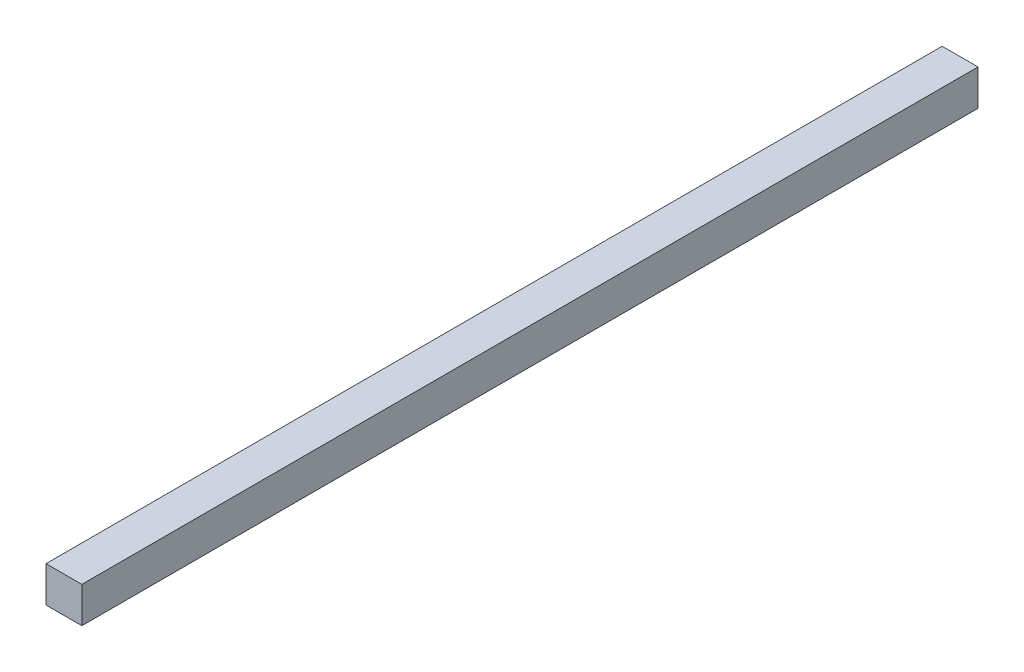
SolidWorks part; units mm, degrees
ref_plane "Front Plane" through (0, 0, 0) normal (0, 0, 1) x (1, 0, 0)
ref_plane "Top Plane" through (0, 0, 0) normal (0, 1, 0) x (1, 0, 0)
ref_plane "Right Plane" through (0, 0, 0) normal (1, 0, 0) x (0, 0, -1)
sketch "Sketch1" plane through (0, 0, 0) normal (0, 0, 1) x (1, 0, 0)
  line L1 (0, 0) -> (25.4, 0)
  line L2 (0, 0) -> (0, 25.4)
  line L3 (0, 25.4) -> (25.4, 25.4)
  line L4 (25.4, 0) -> (25.4, 25.4)
  dimension "D1" = 25.4
  dimension "D2" = 25.4
extrude "Boss-Extrude1" add sketch "Sketch1" along normal blind 635
